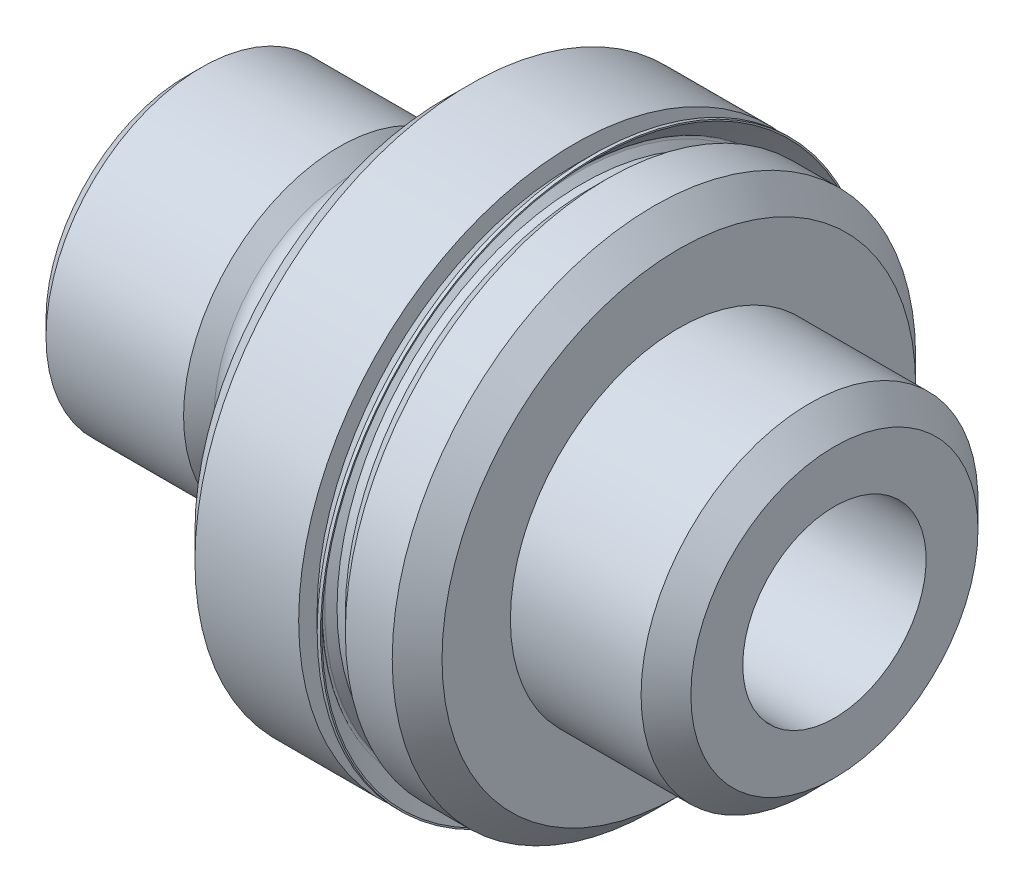
SolidWorks part; units mm, degrees
ref_plane "Front Plane" through (0, 0, 0) normal (0, 0, 1) x (1, 0, 0)
ref_plane "Top Plane" through (0, 0, 0) normal (0, 1, 0) x (1, 0, 0)
ref_plane "Right Plane" through (0, 0, 0) normal (1, 0, 0) x (0, 0, -1)
sketch "Sketch1" plane through (0, 0, 0) normal (0, 0, 1) x (1, 0, 0)
  line L0 (0, 0) -> (0, 8.589)
  line L1 (0, 8.589) -> (0.936, 9.525)
  line L2 (0.936, 9.525) -> (9.3565, 9.525)
  line L3 (9.3565, 9.525) -> (10.2956, 8.594)
  line L4 (11.0109, 8.2995) -> (12.446, 8.2995)
  line L5 (13.462, 9.3154) -> (13.462, 9.4932)
  line L6 (13.462, 9.4932) -> (15.8496, 9.4932)
  line L7 (15.8496, 9.4932) -> (15.8496, 0)
  line L8 (15.8496, 0) -> (0, 0)
  line L9 (15.8496, 0) -> (0, 0) construction
  arc A0 (10.2956, 8.594) -> (11.0109, 8.2995) centre (11.0109, 9.3154) ccw
  arc A1 (12.446, 8.2995) -> (13.462, 9.3154) centre (12.446, 9.3154) ccw
revolve "Revolve1" add sketch "Sketch1" angle 360 about L9 reverse direction yes
cosmetic thread "Cosmetic Thread1" parameters "D1"=10.2925, "D2"=17.178
sketch "Sketch2" plane through (0, 0, 0) normal (0, 0, 1) x (1, 0, 0)
  line L0 (15.8496, 0) -> (15.8496, 15.3226)
  line L1 (15.8496, 15.3226) -> (17.3736, 16.8466)
  line L2 (17.3736, 16.8466) -> (23.7236, 16.8466)
  line L3 (23.7236, 16.8466) -> (23.7236, 15.0051)
  line L4 (23.7236, 15.0051) -> (24.7396, 15.0051)
  line L5 (24.7396, 15.0051) -> (25.7556, 16.021)
  line L6 (25.7556, 16.021) -> (28.6258, 16.021)
  line L7 (28.6258, 16.021) -> (30.1498, 14.4971)
  line L8 (30.1498, 14.4971) -> (30.1498, 0)
  line L9 (30.1498, 0) -> (15.8496, 0)
  line L10 (30.1498, 0) -> (15.8496, 0) construction
revolve "Revolve2" add sketch "Sketch2" angle 360 about L10 reverse direction yes
sketch "Sketch3" plane through (0, 0, 0) normal (0, 0, 1) x (1, 0, 0)
  line L0 (30.1498, 0) -> (30.1498, 10.3124)
  line L1 (30.1498, 10.3124) -> (38.1508, 10.3124)
  line L2 (38.1508, 10.3124) -> (39.6748, 8.7884)
  line L3 (39.6748, 8.7884) -> (39.6748, 0)
  line L4 (39.6748, 0) -> (30.1498, 0)
  line L5 (39.6748, 0) -> (30.1498, 0) construction
revolve "Revolve3" add sketch "Sketch3" angle 360 about L5 reverse direction yes
hole_wizard "Hole1" positions "Sketch5" profile "Sketch4" legacy
sketch "Sketch5" plane through (0, 0, 0) normal (-1, 0, 0) x (0, 0, 1)
  point P0 (0, 0)
sketch "Sketch4" plane through (0, 0, 0) normal (0, 1, 0) x (0, 0, 1)
  line L0 (0, 0) -> (0, 39.6748)
  line L1 (0, 39.6748) -> (5.6134, 39.6748)
  line L2 (5.6134, 39.6748) -> (5.6134, 0.762)
  line L3 (5.6134, 0.762) -> (6.3754, 0)
  line L4 (6.3754, 0) -> (0, 0)
  line L5 (0, -6.4453) -> (0, 115.525) construction
  line L6 (-5.6134, 0.762) -> (-6.3754, 0) construction
  dimension "Diameter" = 11.2268
  dimension "Depth" = 39.6748
  dimension "C-Sink Angle" = 90
  dimension "C-Sink Diameter" = 12.7508
ref_plane "Plane1" through (0, 0, 0) normal (1, 0, 0) x (0, 0, -1)
ref_plane "Plane2" through (0, 0, 0) normal (1, 0, 0) x (0, 0, -1)
ref_plane "Plane3" through (0, 0, 0) normal (0, -0.7071, 0.7071) x (1, 0, 0)
ref_plane "Plane4" through (0, 0, 0) normal (1, 0, 0) x (0, 0, -1)
ref_plane "Plane5" through (23.749, 0, 0) normal (1, 0, 0) x (0, 0, -1)
ref_plane "Plane6" through (15.8496, 0, 0) normal (1, 0, 0) x (0, 0, -1)
ref_plane "Plane7" through (23.749, 0, 0) normal (1, 0, 0) x (0, 0, -1)
sketch "Sketch6" plane through (0, 0, 0) normal (0, 0, 1) x (1, 0, 0)
  line L0 (23.7236, 14.751) -> (24.7396, 14.751)
  line L1 (24.7396, 14.751) -> (24.7396, 15.0051)
  line L2 (24.7396, 15.0051) -> (24.2316, 15.0051)
  line L3 (24.2316, 15.0051) -> (23.857, 15.3797)
  line L4 (23.857, 15.5593) -> (25.0601, 16.7624)
  line L5 (25.0601, 16.7624) -> (25.0601, 16.8466)
  line L6 (25.0601, 16.8466) -> (24.8569, 16.8466)
  line L7 (24.8569, 16.8466) -> (23.7236, 15.7133)
  line L8 (23.7236, 15.7133) -> (23.7236, 14.751)
  line L9 (24.7396, 0) -> (23.7236, 0) construction
  arc A0 (23.857, 15.3797) -> (23.857, 15.5593) centre (23.9468, 15.4695) cw
revolve "Revolve4" add sketch "Sketch6" angle 360 about L9 reverse direction yes
ref_plane "Plane8" through (24.7396, 0, 0) normal (1, 0, 0) x (0, 0, -1)
ref_plane "Plane9" through (15.8496, 0, 0) normal (1, 0, 0) x (0, 0, -1)
ref_plane "Plane10" through (13.462, 0, 0) normal (1, 0, 0) x (0, 0, -1)
ref_plane "Plane11" through (0, 0, 0) normal (0, 1, 0) x (1, 0, 0)
ref_plane "Plane12" through (0, 0, 0) normal (0, 1, 0) x (1, 0, 0)
ref_plane "Plane13" through (15.8496, 0, 0) normal (1, 0, 0) x (0, 0, -1)
ref_plane "Plane14" through (0, 0, 0) normal (0, 1, 0) x (1, 0, 0)
ref_plane "Plane15" through (0, 0, 0) normal (0, 1, 0) x (1, 0, 0)
ref_plane "Plane16" through (0, 0, 0) normal (0, 1, 0) x (1, 0, 0)
ref_plane "Plane17" through (0, 0, 0) normal (1, 0, 0) x (0, 0, -1)
ref_plane "dp1 XY" through (0, 0, 0) normal (0, 0, 1) x (1, 0, 0)
ref_plane "dp1 XZ" through (0, 9.4932, 0) normal (0, -1, 0) x (-1, 0, 0)
ref_plane "dp1 YZ" through (15.8496, 0, 0) normal (1, 0, 0) x (0, 0, -1)
ref_axis "dp1 X" through (-80.9, 9.4932, 0) along (1, 0, 0)
ref_axis "dp1 Y" through (15.8496, -50, 0) along (0, 1, 0)
ref_axis "dp1 Z" through (15.8496, 9.4932, 80.9) along (0, 0, -1)
sketch3d "dp1"
  point P0 (15.8496, 9.4932, 0)
ref_plane "dp2 XY" through (0, 0, 0) normal (0, 0, 1) x (1, 0, 0)
ref_plane "dp2 XZ" through (0, -9.4932, 0) normal (0, -1, 0) x (-1, 0, 0)
ref_plane "dp2 YZ" through (15.8496, 0, 0) normal (1, 0, 0) x (0, 0, -1)
ref_axis "dp2 X" through (-80.9, -9.4932, 0) along (1, 0, 0)
ref_axis "dp2 Y" through (15.8496, -50, 0) along (0, 1, 0)
ref_axis "dp2 Z" through (15.8496, -9.4932, 80.9) along (0, 0, -1)
sketch3d "dp2"
  point P0 (15.8496, -9.4932, 0)
ref_plane "rod_guide XY" through (0, 0, 0) normal (1, 0, 0) x (0, 0, -1)
ref_plane "rod_guide XZ" through (0, 0, 0) normal (0, -1, 0) x (-1, 0, 0)
ref_plane "rod_guide YZ" through (0, 0, 0) normal (0, 0, -1) x (-1, 0, 0)
ref_axis "rod_guide X" through (0, 0, 80.9) along (0, 0, -1)
ref_axis "rod_guide Y" through (0, -50, 0) along (0, 1, 0)
ref_axis "rod_guide Z" through (80.9, 0, 0) along (-1, 0, 0)
sketch3d "rod_guide"
  point P0 (0, 0, 0)
ref_plane "s1 XY" through (0, 0, 0) normal (0, 0, 1) x (1, 0, 0)
ref_plane "s1 XZ" through (0, 0, 0) normal (0, -1, 0) x (-1, 0, 0)
ref_plane "s1 YZ" through (13.462, 0, 0) normal (1, 0, 0) x (0, 0, -1)
ref_axis "s1 X" through (-80.9, 0, 0) along (1, 0, 0)
ref_axis "s1 Y" through (13.462, -50, 0) along (0, 1, 0)
ref_axis "s1 Z" through (13.462, 0, 80.9) along (0, 0, -1)
sketch3d "s1"
  point P0 (13.462, 0, 0)
ref_plane "s2 XY" through (0, 0, 0) normal (0, 0, 1) x (1, 0, 0)
ref_plane "s2 XZ" through (0, 0, 0) normal (0, -1, 0) x (-1, 0, 0)
ref_plane "s2 YZ" through (15.8496, 0, 0) normal (1, 0, 0) x (0, 0, -1)
ref_axis "s2 X" through (-80.9, 0, 0) along (1, 0, 0)
ref_axis "s2 Y" through (15.8496, -50, 0) along (0, 1, 0)
ref_axis "s2 Z" through (15.8496, 0, 80.9) along (0, 0, -1)
sketch3d "s2"
  point P0 (15.8496, 0, 0)
ref_plane "t1 XY" through (15.8496, 0, 0) normal (1, 0, 0) x (0, 0, -1)
ref_plane "t1 XZ" through (0, 0, 0) normal (0, -1, 0) x (-1, 0, 0)
ref_plane "t1 YZ" through (0, 0, 0) normal (0, 0, -1) x (-1, 0, 0)
ref_axis "t1 X" through (15.8496, 0, 80.9) along (0, 0, -1)
ref_axis "t1 Y" through (15.8496, -50, 0) along (0, 1, 0)
ref_axis "t1 Z" through (80.9, 0, 0) along (-1, 0, 0)
sketch3d "t1"
  point P0 (15.8496, 0, 0)
ref_plane "t111 XY" through (15.8496, 0, 0) normal (1, 0, 0) x (0, 0, -1)
ref_plane "t111 XZ" through (0, 0, 0) normal (0, -1, 0) x (-1, 0, 0)
ref_plane "t111 YZ" through (0, 0, 0) normal (0, 0, -1) x (-1, 0, 0)
ref_axis "t111 X" through (15.8496, 0, 80.9) along (0, 0, -1)
ref_axis "t111 Y" through (15.8496, -50, 0) along (0, 1, 0)
ref_axis "t111 Z" through (80.9, 0, 0) along (-1, 0, 0)
sketch3d "t111"
  point P0 (15.8496, 0, 0)
ref_plane "to_foot_bracket XY" through (15.8496, 0, 0) normal (1, 0, 0) x (0, 0, -1)
ref_plane "to_foot_bracket XZ" through (0, 0, 0) normal (0, -1, 0) x (-1, 0, 0)
ref_plane "to_foot_bracket YZ" through (0, 0, 0) normal (0, 0, -1) x (-1, 0, 0)
ref_axis "to_foot_bracket X" through (15.8496, 0, 80.9) along (0, 0, -1)
ref_axis "to_foot_bracket Y" through (15.8496, -50, 0) along (0, 1, 0)
ref_axis "to_foot_bracket Z" through (80.9, 0, 0) along (-1, 0, 0)
sketch3d "to_foot_bracket"
  point P0 (15.8496, 0, 0)
ref_plane "to_nut XY" through (13.462, 0, 0) normal (1, 0, 0) x (0, 0, -1)
ref_plane "to_nut XZ" through (0, 0, 0) normal (0, -1, 0) x (-1, 0, 0)
ref_plane "to_nut YZ" through (0, 0, 0) normal (0, 0, -1) x (-1, 0, 0)
ref_axis "to_nut X" through (13.462, 0, 80.9) along (0, 0, -1)
ref_axis "to_nut Y" through (13.462, -50, 0) along (0, 1, 0)
ref_axis "to_nut Z" through (80.9, 0, 0) along (-1, 0, 0)
sketch3d "to_nut"
  point P0 (13.462, 0, 0)
ref_plane "to_rod XY" through (0, 0, 0) normal (1, 0, 0) x (0, 0, -1)
ref_plane "to_rod XZ" through (0, 0, 0) normal (0, -1, 0) x (-1, 0, 0)
ref_plane "to_rod YZ" through (0, 0, 0) normal (0, 0, -1) x (-1, 0, 0)
ref_axis "to_rod X" through (0, 0, 80.9) along (0, 0, -1)
ref_axis "to_rod Y" through (0, -50, 0) along (0, 1, 0)
ref_axis "to_rod Z" through (80.9, 0, 0) along (-1, 0, 0)
sketch3d "to_rod"
  point P0 (0, 0, 0)
ref_plane "to_screw XY" through (0, 0, 0) normal (0, 1, 0) x (1, 0, 0)
ref_plane "to_screw XZ" through (0, 0, 0) normal (0, 0, 1) x (1, 0, 0)
ref_plane "to_screw YZ" through (23.7998, 0, 0) normal (1, 0, 0) x (0, 0, -1)
ref_axis "to_screw X" through (-80.9, 0, 0) along (1, 0, 0)
ref_axis "to_screw Y" through (23.7998, 0, 50) along (0, 0, -1)
ref_axis "to_screw Z" through (23.7998, 50, 0) along (0, -1, 0)
sketch3d "to_screw"
  point P0 (23.7998, 0, 0)
ref_plane "to_trunnion_brackets XY" through (0, 0, 0) normal (0, 1, 0) x (1, 0, 0)
ref_plane "to_trunnion_brackets XZ" through (0, 0, 0) normal (0, 0, 1) x (1, 0, 0)
ref_plane "to_trunnion_brackets YZ" through (0, 0, 0) normal (1, 0, 0) x (0, 0, -1)
ref_axis "to_trunnion_brackets X" through (-80.9, 0, 0) along (1, 0, 0)
ref_axis "to_trunnion_brackets Y" through (0, 0, 50) along (0, 0, -1)
ref_axis "to_trunnion_brackets Z" through (0, 50, 0) along (0, -1, 0)
sketch3d "to_trunnion_brackets"
  point P0 (0, 0, 0)
ref_plane "to_trunnion_brackets1 XY" through (0, 0, 0) normal (0, 1, 0) x (1, 0, 0)
ref_plane "to_trunnion_brackets1 XZ" through (0, 0, 0) normal (0, 0, 1) x (1, 0, 0)
ref_plane "to_trunnion_brackets1 YZ" through (0, 0, 0) normal (1, 0, 0) x (0, 0, -1)
ref_axis "to_trunnion_brackets1 X" through (-80.9, 0, 0) along (1, 0, 0)
ref_axis "to_trunnion_brackets1 Y" through (0, 0, 50) along (0, 0, -1)
ref_axis "to_trunnion_brackets1 Z" through (0, 50, 0) along (0, -1, 0)
sketch3d "to_trunnion_brackets1"
  point P0 (0, 0, 0)
ref_plane "to_trunnion_brackets2 XY" through (0, 0, 0) normal (0, 1, 0) x (1, 0, 0)
ref_plane "to_trunnion_brackets2 XZ" through (0, 0, 0) normal (0, 0, 1) x (1, 0, 0)
ref_plane "to_trunnion_brackets2 YZ" through (0, 0, 0) normal (1, 0, 0) x (0, 0, -1)
ref_axis "to_trunnion_brackets2 X" through (-80.9, 0, 0) along (1, 0, 0)
ref_axis "to_trunnion_brackets2 Y" through (0, 0, 50) along (0, 0, -1)
ref_axis "to_trunnion_brackets2 Z" through (0, 50, 0) along (0, -1, 0)
sketch3d "to_trunnion_brackets2"
  point P0 (0, 0, 0)
ref_plane "to_tube XY" through (24.7396, 0, 0) normal (1, 0, 0) x (0, 0, -1)
ref_plane "to_tube XZ" through (0, 0, 0) normal (0, -1, 0) x (-1, 0, 0)
ref_plane "to_tube YZ" through (0, 0, 0) normal (0, 0, -1) x (-1, 0, 0)
ref_axis "to_tube X" through (24.7396, 0, 80.9) along (0, 0, -1)
ref_axis "to_tube Y" through (24.7396, -50, 0) along (0, 1, 0)
ref_axis "to_tube Z" through (80.9, 0, 0) along (-1, 0, 0)
sketch3d "to_tube"
  point P0 (24.7396, 0, 0)
